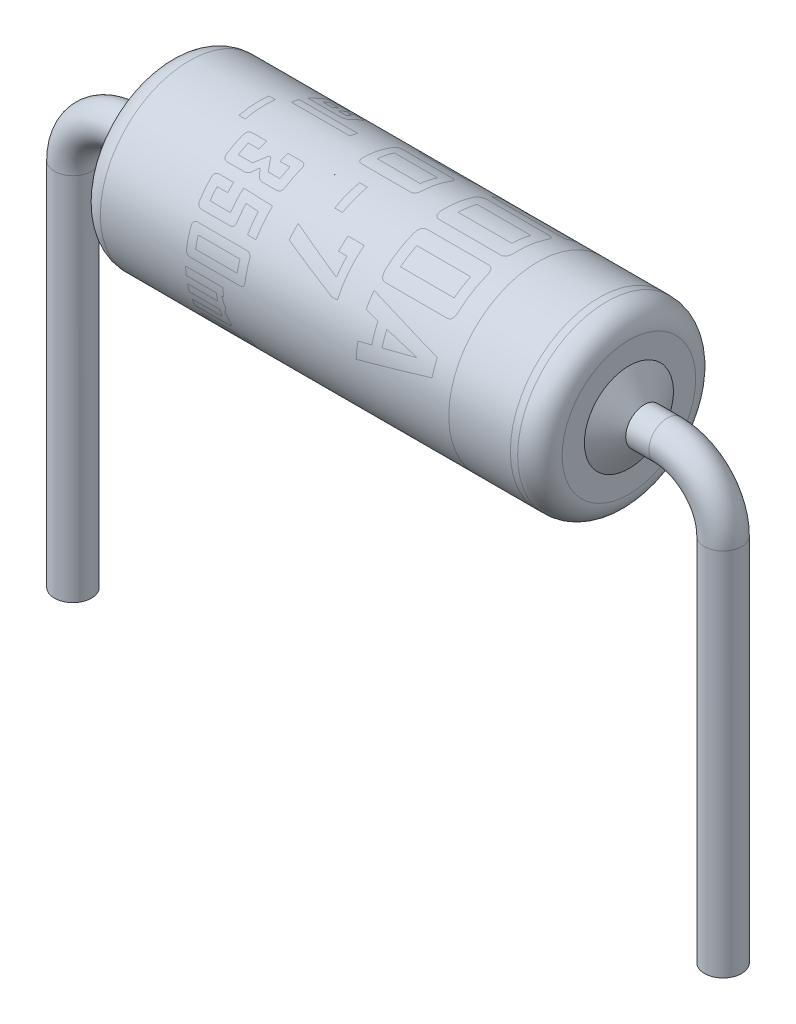
SolidWorks part; units mm, degrees
ref_plane "Front Plane" through (0, 0, 0) normal (0, 0, 1) x (1, 0, 0)
ref_plane "Top Plane" through (0, 0, 0) normal (0, 1, 0) x (1, 0, 0)
ref_plane "Right Plane" through (0, 0, 0) normal (1, 0, 0) x (0, 0, -1)
ref_plane "BODY_RPlane" through (4.445, 0, 0) normal (1, 0, 0) x (0, 0, -1)
sketch "Sketch10" plane through (0, 0, 0) normal (0, 0, 1) x (1, 0, 0)
  line L0 (1.0775, 2.2175) -> (7.8125, 2.2175) construction
  line L1 (4.445, -1.2109) -> (4.445, 1.2109) construction
  line L2 (1.2875, 2.8263) -> (4.445, 2.8263) construction
  line L3 (1.2875, 3.1245) -> (1.2875, 2.5332) construction
  line L4 (1.5919, 3.435) -> (7.2981, 3.435)
  line L6 (1.2875, 3.1306) -> (1.2875, 2.8263)
  line L7 (1.2875, 2.8263) -> (7.6025, 2.8263)
  line L8 (7.6025, 3.1306) -> (7.6025, 2.8263)
  arc A2 (1.5919, 3.435) -> (1.2875, 3.1306) centre (1.5919, 3.1306) ccw
  arc A3 (7.2981, 3.435) -> (7.6025, 3.1306) centre (7.2981, 3.1306) cw
  point P2 (4.445, 2.2175)
  point P14 (4.445, 3.435)
  point P15 (4.445, 2.8263)
  point P18 (4.445, 3.435)
  dimension "D6" = 0.3044
  dimension "D1" = 2.2175
  dimension "D2" = 6.735
  dimension "D4" = 1.2175
  dimension "D5" = 0.21
  dimension "D3" = 0.6088
revolve "BODY_main" add sketch "Sketch10" angle 360 about L0
sketch "Sketch11" plane through (0, 0, 0) normal (0, 0, 1) x (1, 0, 0)
  line L0 (1.0775, 2.2175) -> (1.0775, 2.4715)
  line L1 (1.0775, 2.4715) -> (1.2875, 2.8263)
  line L2 (1.2875, 2.8263) -> (1.4875, 2.8263)
  line L3 (1.0775, 2.2175) -> (1.4875, 2.2175)
  line L5 (1.4875, 2.2175) -> (1.4875, 2.8263)
  line L9 (4.445, -1.2109) -> (4.445, 1.2109) construction
  line L12 (7.4025, 2.2175) -> (7.4025, 2.8263)
  line L13 (7.8125, 2.2175) -> (7.4025, 2.2175)
  line L14 (7.6025, 2.8263) -> (7.4025, 2.8263)
  line L15 (7.8125, 2.4715) -> (7.6025, 2.8263)
  line L16 (7.8125, 2.2175) -> (7.8125, 2.4715)
  dimension "D1" = 0.254
revolve "BODY_to_PIN" add sketch "Sketch11" angle 360 about L0
ref_plane "TEXT_plane" through (0, 3.535, 0) normal (0, 1, 0) x (1, 0, 0)
sketch "Sketch4"
  dimension "D4" = 8.89
  dimension "D1" = 7.6498
  dimension "D3" = 0.8419
  dimension "D5" = 0.1
  dimension "D6" = 0.1
  dimension "D2" = 5
wrap "TEXT_Wrap" sketch "Sketch4" wrap type scribe source sketch "Sketch4" face at (1.5919, 2.2175, 1.2175)
sketch "Sketch6" plane through (4.445, 0, 0) normal (1, 0, 0) x (0, 0, -1)
  circle A0 centre (0, 2.2175) radius 0.254
  dimension "D1" = 0.508
sketch "Sketch7" plane through (0, 0, 0) normal (0, 0, 1) x (1, 0, 0)
  line L0 (8.128, 2.2175) -> (0.762, 2.2175)
  line L1 (0, 1.4555) -> (0, -3.6)
  line L2 (4.445, 2.2175) -> (4.445, -3.6) construction
  line L3 (0, -3.6) -> (4.445, -3.6) construction
  line L5 (4.445, -1.2109) -> (4.445, 1.2109) construction
  line L6 (8.89, 1.4555) -> (8.89, -3.6)
  line L9 (1.0775, 2.2175) -> (7.8125, 2.2175) construction
  arc A0 (0.762, 2.2175) -> (0, 1.4555) centre (0.762, 1.4555) ccw
  arc A1 (8.128, 2.2175) -> (8.89, 1.4555) centre (8.128, 1.4555) cw
  dimension "D3" = 0.762
  dimension "D1" = 3.6
sweep "PINS" add profiles "Sketch6" path "Sketch7"
equation "\"D4@Sketch7\"=\"PIN_PITCH\""
equation "\"pin_config-----------------\"= 0x000000000000000000000000000000000"
equation "\"PIN_PITCH\" = 350mil"
equation "\"PCB_standoff\"= 1mm"
equation "\"PCB_thickness\"= 1.6mm"
equation "\"PCB_bottom_lead\"= 1.0mm"
equation "\"PIN_C_max\"= 0.558mm"
equation "\"PIN_C_min\"= 0.458mm"
equation "\"body_config----------------\"= 0x000000000000000000000000000000000"
equation "\"BODY_B_max\"= 7.62mm"
equation "\"BODY_B_min\"= 5.85mm"
equation "\"BODY_D_max\"= 2.71mm"
equation "\"BODY_D_min\"= 2.16mm"
equation "\"part_config----------------\"= 0x000000000000000000000000000000000"
equation "\"Component_Size\" = 1"
equation "\"Component_Type\"= 0'variable is not used"
equation "\"auto_calc-------------------\"= 0x000000000000000000000000000000000"
equation "\"BODY_B\"= IIF ( \"Component_Size\" > 0 , IIF ( \"Component_Size\" = 1 , ( ( \"BODY_B_max\" + \"BODY_B_min\" ) / 2 ) , \"BODY_B_max\" ) , \"BODY_B_min\" )'NOT_FOR_USER , AUTOMATIC CALCULATION"
equation "\"BODY_D\"= IIF ( \"Component_Size\" > 0 , IIF ( \"Component_Size\" = 1 , ( ( \"BODY_D_max\" + \"BODY_D_min\" ) / 2 ) , \"BODY_D_max\" ) , \"BODY_D_min\" )'NOT_FOR_USER , AUTOMATIC CALCULATION"
equation "\"PIN_C\"= IIF ( \"Component_Size\" > 0 , IIF ( \"Component_Size\" = 1 , ( ( \"PIN_C_max\" + \"PIN_C_min\" ) / 2 ) , \"PIN_C_max\" ) , \"PIN_C_min\" )'NOT_FOR_USER , AUTOMATIC CALCULATION"
equation "\"PIN_L\"= \"PCB_standoff\" + \"PCB_thickness\" + \"PCB_bottom_lead\"'NOT_FOR_USER , AUTOMATIC CALCULATION"
equation "\"PIN_R\"= \"PIN_C\" * 1.5'NOT_FOR_USER , AUTOMATIC CALCULATION"
equation "\"D1@BODY_RPlane\" = \"PIN_PITCH\" / 2"
equation "\"D1@TEXT_plane\"=\"BODY_D\"+\"PCB_standoff\"+0.1"
equation "\"D1@Sketch4\"=\"BODY_D\" * pi"
equation "\"BODY_CATM_H1\"= \"BODY_B\" / 8'NOT_FOR_USER , AUTOMATIC CALCULATION"
equation "\"D4@Sketch4\"=\"PIN_PITCH\""
equation "\"D1@Sketch6\"=\"PIN_C\""
equation "\"D3@Sketch7\"=\"PIN_R\""
equation "\"D1@Sketch7\"=\"PIN_L\""
equation "\"D2@Sketch10\"=\"BODY_B\""
equation "\"D1@Sketch10\"=(\"BODY_D\" / 2) + \"PCB_standoff\""
equation "\"D4@Sketch10\"=\"BODY_D\"/2"
equation "\"D1@Sketch11\"=\"PIN_C\"/2"
equation "\"D3@Sketch4\"=\"BODY_CATM_H1\""
equation "\"D3@Sketch10\"=\"BODY_D\"/4"
equation "\"D6@Sketch10\"=\"BODY_D\"/8"
